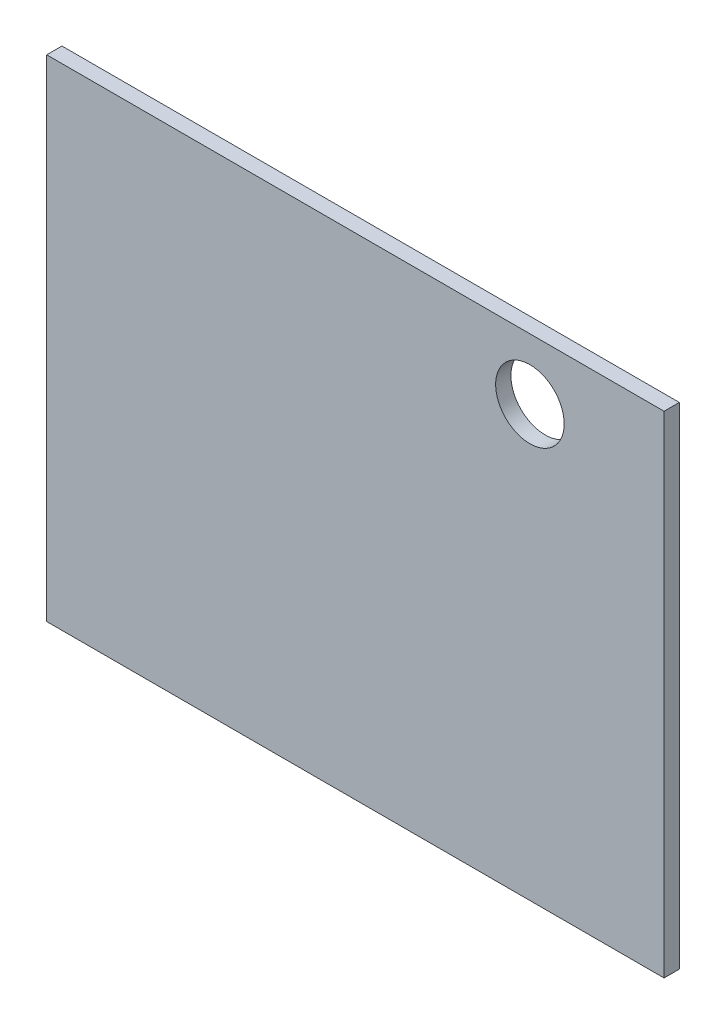
SolidWorks part; units mm, degrees
ref_plane "Front Plane" through (0, 0, 0) normal (0, 0, 1) x (1, 0, 0)
ref_plane "Top Plane" through (0, 0, 0) normal (0, 1, 0) x (1, 0, 0)
ref_plane "Right Plane" through (0, 0, 0) normal (1, 0, 0) x (0, 0, -1)
sketch "Sketch1" plane through (0, 0, 0) normal (0, 0, 1) x (1, 0, 0)
  line L1 (-128.5875, -102.235) -> (128.5875, -102.235)
  line L2 (-128.5875, -102.235) -> (-128.5875, 102.235)
  line L3 (-128.5875, 102.235) -> (128.5875, 102.235)
  line L4 (128.5875, -102.235) -> (128.5875, 102.235)
  line L5 (-128.5875, -102.235) -> (128.5875, 102.235) construction
  line L6 (-128.5875, 102.235) -> (128.5875, -102.235) construction
  point P0 (0, 0)
  dimension "D1" = 257.175
  dimension "D2" = 204.47
extrude "Boss-Extrude1" add sketch "Sketch1" along normal blind 6.35
sketch "Sketch2" plane through (0, 0, 6.35) normal (0, 0, 1) x (1, 0, 0)
  line L0 (128.5875, 102.235) -> (-128.5875, 102.235) construction
  line L1 (128.5875, -102.235) -> (128.5875, 102.235) construction
  circle A0 centre (72.7075, 76.835) radius 14.2748
  dimension "D3" = 28.5496
  dimension "D1" = 25.4
  dimension "D2" = 55.88
extrude "Cut-Extrude1" cut sketch "Sketch2" against normal through all
